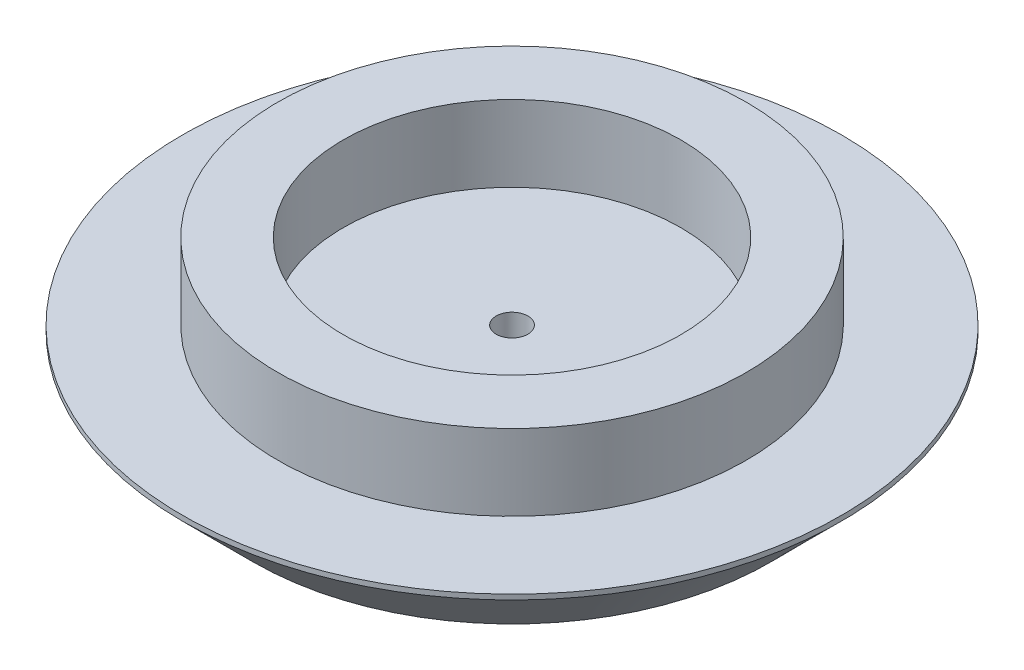
SolidWorks part; units mm, degrees
material "PE Low/Medium Density"
ref_plane "Front Plane" through (0, 0, 0) normal (0, 0, 1) x (1, 0, 0)
ref_plane "Top Plane" through (0, 0, 0) normal (0, 1, 0) x (1, 0, 0)
ref_plane "Right Plane" through (0, 0, 0) normal (1, 0, 0) x (0, 0, -1)
sketch "Sketch1" plane through (0, 0, 0) normal (0, 0, 1) x (1, 0, 0)
  line L0 (-29.337, 0) -> (-41.275, 0)
  line L1 (-29.337, 0) -> (-29.337, 9.525)
  line L2 (-29.337, 9.525) -> (-21.1455, 9.525)
  line L3 (-21.1455, 9.525) -> (-21.1455, 0)
  line L4 (-21.1455, 0) -> (0, 0)
  line L5 (-41.275, 0) -> (-41.275, -9.525)
  line L6 (-41.275, -9.525) -> (0, -9.525)
  line L7 (0, -9.525) -> (0, 0)
  dimension "D1" = 9.525
  dimension "D2" = 9.525
  dimension "D3" = 21.1455
  dimension "D4" = 29.337
  dimension "D5" = 41.275
revolve "Revolve1" add sketch "Sketch1" angle 360 about L7
chamfer "Chamfer1" distance 8.89 angle 45 1 edges at (0, -9.525, -41.275)
sketch "Sketch9" plane through (0, -9.525, 0) normal (0, -1, 0) x (1, 0, 0)
  line L0 (0, 0) -> (0, 32.385) construction
  circle A0 centre (0, 0) radius 32.385 construction
hole_wizard "5/32 (0.15625) Diameter Hole1" positions "3DSketch5" profile "Sketch11" hole size "5/32" standard "Ansi Inch" end condition up to next
sketch3d "3DSketch5"
  point P0 (0, -9.525, 0)
sketch "Sketch11" plane through (0, -9.525, 0) normal (1, 0, 0) x (0, 0, -1)
  line L0 (0, 0) -> (0, 9.525)
  line L1 (0, 9.525) -> (1.9844, 9.525)
  line L2 (1.9844, 9.525) -> (1.9844, 0)
  line L5 (1.9844, 0) -> (0, 0)
  line L11 (0, -6.35) -> (0, 107.95) construction
  dimension "Thru Hole Dia." = 3.9688
  dimension "Thru Hole Depth" = 9.525
